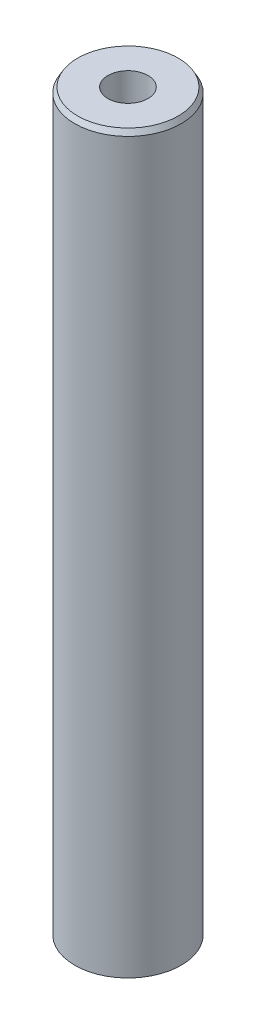
SolidWorks part; units mm, degrees
ref_plane "Front Plane" through (0, 0, 0) normal (0, 0, 1) x (1, 0, 0)
ref_plane "Top Plane" through (0, 0, 0) normal (0, 1, 0) x (1, 0, 0)
ref_plane "Right Plane" through (0, 0, 0) normal (1, 0, 0) x (0, 0, -1)
sketch "Sketch1" plane through (0, 0, 0) normal (0, 1, 0) x (1, 0, 0)
  circle A0 centre (0, 0) radius 7.5
  dimension "SHAFT_OD" = 15
extrude "Boss-Extrude1" add sketch "Sketch1" along normal blind 103.8636
sketch "Sketch2" plane through (0, 0, 0) normal (0, 1, 0) x (1, 0, 0)
  circle A0 centre (0, 0) radius 2.824
  dimension "BORE_D" = 5.6479
extrude "Cut-Extrude1" cut sketch "Sketch2" along normal through all
chamfer "Chamfer1" distance 0.7257 angle 30 2 edges at (0, 103.8636, 7.5) (0, 0, 7.5) first distance on face at (0, 103.8636, 7.5) first distance on face at (0, 0, 2.824)
